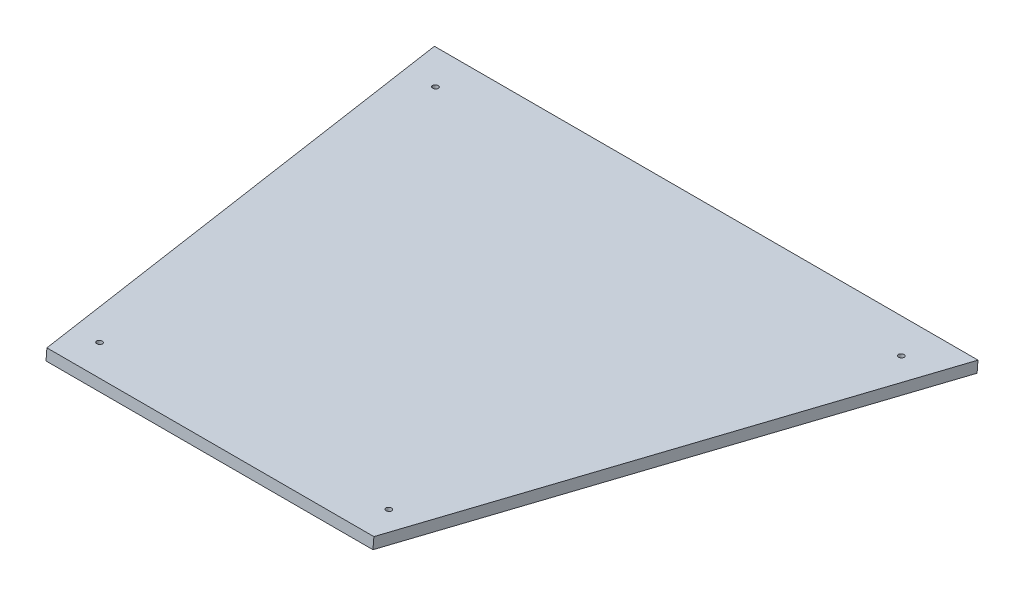
SolidWorks part; units mm, degrees
ref_plane "Front Plane" through (0, 0, 0) normal (0, 0, 1) x (1, 0, 0)
ref_plane "Top Plane" through (0, 0, 0) normal (0, 1, 0) x (1, 0, 0)
ref_plane "Right Plane" through (0, 0, 0) normal (1, 0, 0) x (0, 0, -1)
ref_plane "Plane1" through (-0.0007, -8154.0727, 672.6577) normal (0, -0.9966, 0.0822) x (-1, 0, 0)
sketch "Sketch1" plane through (-0.0007, -8154.0727, 672.6577) normal (0, -0.9966, 0.0822) x (-1, 0, 0)
  line L0 (927.9324, -1893.2884) -> (1306.8393, -1893.2884)
  line L1 (1306.8393, -1893.2884) -> (1432.3521, -1316.7398)
  line L2 (1432.3521, -1316.7398) -> (802.4196, -1316.7398)
  line L3 (802.4196, -1316.7398) -> (927.9324, -1893.2884)
  line L4 (802.4183, -1316.7398) -> (1432.3534, -1316.7398) construction
  line L5 (928.076, -1893.948) -> (801.0629, -1310.5075) construction
  line L6 (1433.7088, -1310.5075) -> (1306.6957, -1893.948) construction
  line L7 (1306.8419, -1893.2884) -> (927.9298, -1893.2884) construction
extrude "Boss-Extrude1" add sketch "Sketch1" along normal blind 12.7
sketch "Sketch2" plane through (-0.0007, -8154.0727, 672.6577) normal (0, 0.9966, -0.0822) x (1, 0, 0)
  line L0 (-927.9324, -1893.2884) -> (-1306.8393, -1893.2884) construction
  line L1 (-1306.8393, -1893.2884) -> (-1432.3521, -1316.7398) construction
  line L2 (-802.4196, -1316.7398) -> (-927.9324, -1893.2884) construction
  line L3 (-1432.3521, -1316.7398) -> (-802.4196, -1316.7398) construction
  circle A0 centre (-1284.9566, -1854.0196) radius 3.175
  circle A3 centre (-949.7975, -1853.9387) radius 3.175
  circle A4 centre (-1387.3011, -1360.7012) radius 3.175
  circle A6 centre (-847.4706, -1360.7012) radius 3.175
  dimension "D1" = 6.35
  dimension "D2" = 39.2688
  dimension "D3" = 29.735
  dimension "D4" = 6.35
  dimension "D5" = 39.3497
  dimension "D7" = 6.35
  dimension "D10" = 6.35
  dimension "D6" = 29.735
  dimension "D8" = 43.9614
  dimension "D9" = 34.6688
  dimension "D11" = 34.6688
  dimension "D12" = 43.9614
extrude "Cut-Extrude1" cut sketch "Sketch2" against normal through all
